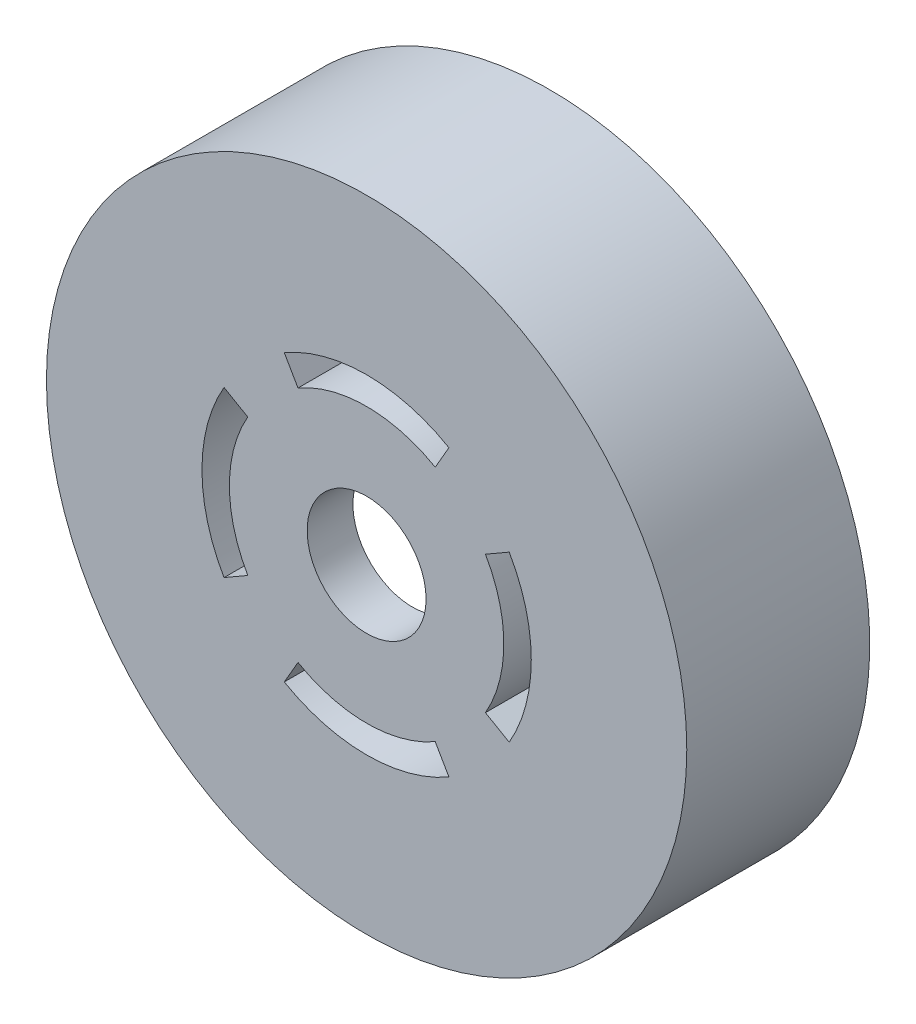
SolidWorks part; units mm, degrees
ref_plane "前视基准面" through (0, 0, 0) normal (0, 0, 1) x (1, 0, 0)
ref_plane "上视基准面" through (0, 0, 0) normal (0, 1, 0) x (1, 0, 0)
ref_plane "右视基准面" through (0, 0, 0) normal (1, 0, 0) x (0, 0, -1)
other "Configuration Table"
sketch "草图2" plane through (0, 0, 0) normal (0, 0, 1) x (1, 0, 0)
  circle A0 centre (0, 0) radius 35
  circle A1 centre (0, 0) radius 6.5
  dimension "D1" = 70
  dimension "D2" = 13
extrude "凸台-拉伸1" add sketch "草图2" along normal blind 5
sketch "草图3" plane through (0, 0, 0) normal (0, 0, -1) x (-1, 0, 0)
  circle A0 centre (0, 0) radius 30.1
  circle A1 centre (0, 0) radius 35
  dimension "D1" = 60.2
extrude "凸台-拉伸2" add sketch "草图3" along normal blind 15
sketch "草图4" plane through (0, 0, -15) normal (0, 0, -1) x (-1, 0, 0)
  line L0 (0, 0) -> (0, 32.5)
  line L1 (0, 0) -> (32.5, 0)
  line L2 (0, 0) -> (0, -32.5)
  line L3 (0, 0) -> (-32.5, 0)
  circle A0 centre (0, 32.5) radius 1.55
  circle A1 centre (32.5, 0) radius 1.55
  circle A2 centre (0, -32.5) radius 1.55
  circle A3 centre (-32.5, 0) radius 1.55
  point P9 (0, 0)
  point P17 (0, 0)
  dimension "D2" = 4
  dimension "D1" = 4
extrude "切除-拉伸1" cut sketch "草图4" against normal blind 10 contours A0 | A1 | A2 | A3 region at (1.065, 33.565, -15) region at (-32.5, 1.5062, -15) region at (-1.065, -31.435, -15) region at (34.0062, 0, -15)
sketch "草图5" plane through (0, 0, 0) normal (0, 0, -1) x (-1, 0, 0)
  line L0 (12.9904, -7.5) -> (15.5885, -9)
  line L1 (12.9904, 7.5) -> (15.5885, 9)
  line L2 (-7.5, 12.9904) -> (-9, 15.5885)
  line L3 (7.5, 12.9904) -> (9, 15.5885)
  line L4 (-7.5, -12.9904) -> (-9, -15.5885)
  line L5 (7.5, -12.9904) -> (9, -15.5885)
  line L6 (-12.9904, 7.5) -> (-15.5885, 9)
  line L7 (-12.9904, -7.5) -> (-15.5885, -9)
  arc A1 (7.5, 12.9904) -> (-7.5, 12.9904) centre (0, 0) ccw
  arc A2 (9, 15.5885) -> (-9, 15.5885) centre (0, 0) ccw
  arc A3 (12.9904, -7.5) -> (12.9904, 7.5) centre (0, 0) ccw
  arc A4 (15.5885, -9) -> (15.5885, 9) centre (0, 0) ccw
  arc A5 (-7.5, -12.9904) -> (7.5, -12.9904) centre (0, 0) ccw
  arc A6 (-9, -15.5885) -> (9, -15.5885) centre (0, 0) ccw
  arc A7 (-12.9904, 7.5) -> (-12.9904, -7.5) centre (0, 0) ccw
  arc A8 (-15.5885, 9) -> (-15.5885, -9) centre (0, 0) ccw
  point P21 (0, 0)
  dimension "D1" = 4
extrude "切除-拉伸2" cut sketch "草图5" against normal through all
sketch "草图9" plane through (0, 0, -15) normal (0, 0, -1) x (-1, 0, 0)
  line L0 (0, 0) -> (0, 32.5) construction
  line L1 (0, 0) -> (-21.2839, 21.2839) construction
  circle A0 centre (0, 0) radius 30.1 construction
  arc A1 (-22.0133, 20.5286) -> (-20.5286, 22.0133) centre (-21.2839, 21.2839) cw
  arc A2 (20.5286, 22.0133) -> (22.0133, 20.5286) centre (21.2839, 21.2839) cw
  arc A3 (22.0133, -20.5286) -> (20.5286, -22.0133) centre (21.2839, -21.2839) cw
  arc A4 (-20.5286, -22.0133) -> (-22.0133, -20.5286) centre (-21.2839, -21.2839) cw
  arc A5 (-20.5286, 22.0133) -> (-22.0133, 20.5286) centre (0, 0) ccw
  arc A6 (-22.0133, -20.5286) -> (-20.5286, -22.0133) centre (0, 0) ccw
  arc A7 (20.5286, -22.0133) -> (22.0133, -20.5286) centre (0, 0) ccw
  arc A8 (22.0133, 20.5286) -> (20.5286, 22.0133) centre (0, 0) ccw
  point P21 (0, 0)
  dimension "D2" = 1.05
  dimension "D1" = 45
  dimension "D3" = 4
extrude "切除-拉伸5" cut sketch "草图9" against normal up to surface (15 mm away) up to face at (0, 15.3947, 0)
fillet "圆角1" radius 1 4 edges at (0, -30.1, -15) (-30.1, 0, -15) (0, 30.1, -15) (30.1, 0, -15)
